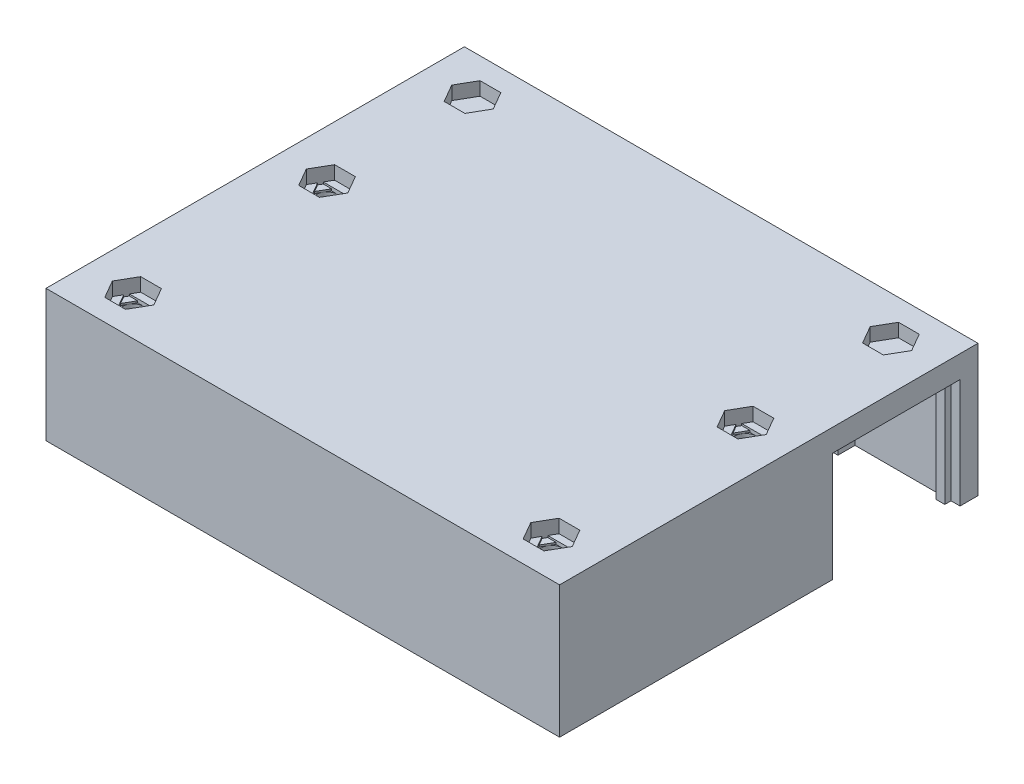
SolidWorks part; units mm, degrees
ref_plane "Front Plane" through (0, 0, 0) normal (0, 0, 1) x (1, 0, 0)
ref_plane "Top Plane" through (0, 0, 0) normal (0, 1, 0) x (1, 0, 0)
ref_plane "Right Plane" through (0, 0, 0) normal (1, 0, 0) x (0, 0, -1)
sketch "Sketch1" plane through (0, 0, 0) normal (0, 1, 0) x (1, 0, 0)
  line L0 (-5.85, 7.1) -> (-5.85, -7.1)
  line L1 (-4.85, -7.1) -> (4.85, -7.1)
  line L2 (-4.85, -7.1) -> (-4.85, 7.1)
  line L3 (-4.85, 7.1) -> (4.85, 7.1)
  line L4 (4.85, -7.1) -> (4.85, 7.1)
  line L5 (-4.85, -7.1) -> (4.85, 7.1)
  line L6 (-4.85, 7.1) -> (4.85, -7.1) construction
  line L7 (0.95, -5.2) -> (8.75, -5.2)
  line L8 (0.95, -5.2) -> (0.95, 5.2)
  line L9 (0.95, 5.2) -> (8.75, 5.2)
  line L10 (8.75, -5.2) -> (8.75, 5.2)
  line L11 (0.95, -5.2) -> (8.75, 5.2) construction
  line L12 (0.95, 5.2) -> (8.75, -5.2) construction
  line L13 (-4.85, 7.1) -> (-6.85, 7.1)
  line L14 (-4.85, 7.1) -> (-4.85, -7.1)
  line L15 (-4.85, -7.1) -> (-6.85, -7.1)
  line L16 (-6.85, 7.1) -> (-6.85, -7.1)
  line L17 (-6.85, 9.1) -> (-6.85, 7.1)
  line L18 (-6.85, 9.1) -> (6.85, 9.1)
  line L19 (6.85, 9.1) -> (6.85, 7.2)
  line L20 (6.85, 7.2) -> (10.75, 7.2)
  line L21 (10.75, 7.2) -> (10.75, -7.2)
  line L22 (10.75, -7.2) -> (6.85, -7.2)
  line L23 (6.85, -7.2) -> (6.85, -9.1)
  line L24 (6.85, -9.1) -> (-6.85, -9.1)
  line L25 (-6.85, -9.1) -> (-6.85, -7.1)
  line L26 (-4.85, 0) -> (-5.85, 0) construction
  line L27 (-5.85, 6.4) -> (-4.85, 6.4)
  line L28 (-5.85, -6.4) -> (-4.85, -6.4)
  line L29 (-5.35, -6.4) -> (-5.35, 0) construction
  line L30 (-5.35, 0) -> (-5.35, 6.4) construction
  line L31 (-5.85, 7.1) -> (-5.85, 9.1)
  line L32 (-5.85, -7.1) -> (-5.85, -9.1)
  line L33 (21.75, -9.1) -> (21.75, 5.2) construction
  line L38 (-6.85, -37.5) -> (50.35, -37.5)
  line L40 (-6.85, -37.5) -> (-6.85, -9.1)
  line L42 (-6.85, -9.1) -> (50.35, -9.1)
  line L43 (50.35, -37.5) -> (50.35, -9.1)
  line L45 (21.75, -37.5) -> (21.75, -22.3) construction
  line L47 (46.25, -11.5) -> (47.25, -11.5) construction
  line L48 (42.55, -5.2) -> (34.75, -5.2)
  line L49 (34.75, -5.2) -> (34.75, 5.2)
  line L50 (42.55, 5.2) -> (34.75, 5.2)
  line L51 (38.65, -7.1) -> (38.65, 7.1)
  line L52 (49.35, 6.4) -> (48.35, 6.4)
  line L53 (48.35, -7.1) -> (48.35, 7.1)
  line L54 (49.35, -6.4) -> (48.35, -6.4)
  line L55 (48.35, -7.1) -> (38.65, -7.1)
  line L56 (49.35, -7.1) -> (49.35, -9.1)
  line L57 (49.35, 7.1) -> (49.35, -7.1)
  line L58 (48.35, 7.1) -> (38.65, 7.1)
  line L59 (49.35, 7.1) -> (49.35, 9.1)
  line L60 (50.35, 9.1) -> (50.35, 7.1)
  line L61 (50.35, 7.1) -> (50.35, -7.1)
  line L62 (50.35, -9.1) -> (50.35, -7.1)
  line L63 (36.65, -9.1) -> (50.35, -9.1)
  line L64 (36.65, -7.2) -> (36.65, -9.1)
  line L65 (32.75, -7.2) -> (36.65, -7.2)
  line L66 (32.75, 7.2) -> (32.75, -7.2)
  line L67 (36.65, 7.2) -> (32.75, 7.2)
  line L68 (36.65, 9.1) -> (36.65, 7.2)
  line L69 (50.35, 9.1) -> (36.65, 9.1)
  line L70 (48.35, -9.1) -> (-4.85, -9.1)
  line L75 (48.35, -9.1) -> (48.35, -35.5)
  line L76 (48.35, -35.5) -> (-4.85, -35.5)
  line L81 (-4.85, -9.1) -> (-4.85, -35.5)
  line L82 (48.35, -9.1) -> (-4.85, -35.5) construction
  line L83 (48.35, -35.5) -> (-4.85, -9.1) construction
  line L84 (6.85, 9.1) -> (36.65, 9.1)
  line L85 (-1.55, -33.1) -> (45.05, -33.1) construction
  line L86 (-1.55, -33.1) -> (-1.55, -11.5) construction
  line L87 (48.35, -7.1) -> (50.35, -7.1)
  line L88 (48.35, 7.1) -> (50.35, 7.1)
  line L89 (-1.55, -11.5) -> (45.05, -11.5) construction
  line L90 (45.05, -33.1) -> (45.05, -11.5) construction
  line L91 (-1.55, -33.1) -> (45.05, -11.5) construction
  line L92 (-1.55, -11.5) -> (45.05, -33.1) construction
  line L93 (47.25, -35.3) -> (-3.75, -35.3) construction
  line L94 (47.25, -35.3) -> (47.25, -9.3) construction
  line L95 (47.25, -9.3) -> (-3.75, -9.3) construction
  line L96 (-3.75, -35.3) -> (-3.75, -9.3) construction
  line L97 (47.25, -35.3) -> (-3.75, -9.3) construction
  line L98 (47.25, -9.3) -> (-3.75, -35.3) construction
  line L99 (45.05, -10.3) -> (45.05, -9.3) construction
  line L101 (-2.55, -13.7) -> (-0.55, -13.7)
  line L102 (-2.55, -13.7) -> (-2.55, -15.7)
  line L103 (-2.55, -15.7) -> (-0.55, -15.7)
  line L104 (-0.55, -13.7) -> (-0.55, -15.7)
  line L105 (-2.55, -13.7) -> (-0.55, -15.7) construction
  line L106 (-2.55, -15.7) -> (-0.55, -13.7) construction
  line L107 (-2.55, -28.9) -> (-0.55, -28.9)
  line L108 (-2.55, -28.9) -> (-2.55, -30.9)
  line L109 (-2.55, -30.9) -> (-0.55, -30.9)
  line L110 (-0.55, -28.9) -> (-0.55, -30.9)
  line L111 (-2.55, -28.9) -> (-0.55, -30.9) construction
  line L112 (-2.55, -30.9) -> (-0.55, -28.9) construction
  line L113 (46.05, -28.9) -> (44.05, -28.9)
  line L114 (46.05, -28.9) -> (46.05, -30.9)
  line L115 (46.05, -30.9) -> (44.05, -30.9)
  line L116 (44.05, -28.9) -> (44.05, -30.9)
  line L117 (46.05, -28.9) -> (44.05, -30.9) construction
  line L118 (46.05, -30.9) -> (44.05, -28.9) construction
  line L119 (46.05, -13.7) -> (44.05, -13.7)
  line L120 (46.05, -13.7) -> (46.05, -15.7)
  line L121 (46.05, -15.7) -> (44.05, -15.7)
  line L122 (44.05, -13.7) -> (44.05, -15.7)
  line L123 (46.05, -13.7) -> (44.05, -15.7) construction
  line L124 (46.05, -15.7) -> (44.05, -13.7) construction
  line L125 (45.05, -29.9) -> (-1.55, -29.9)
  line L126 (45.05, -29.9) -> (45.05, -14.7)
  line L127 (45.05, -14.7) -> (-1.55, -14.7)
  line L128 (-1.55, -29.9) -> (-1.55, -14.7)
  line L129 (45.05, -29.9) -> (-1.55, -14.7) construction
  line L130 (45.05, -14.7) -> (-1.55, -29.9) construction
  circle A0 centre (-1.55, -11.5) radius 1.2
  circle A1 centre (-1.55, -33.1) radius 1.2
  circle A2 centre (45.05, -33.1) radius 1.2
  circle A3 centre (45.05, -11.5) radius 1.2
  point P0 (0, 0)
  point P6 (4.85, 0)
  point P88 (-1.55, -14.7)
  point P93 (-1.55, -29.9)
  point P98 (45.05, -29.9)
  point P103 (45.05, -14.7)
  point P108 (45.05, -17.403)
  point P109 (45.05, -27.197)
  point P114 (-1.55, -27.197)
  dimension "D20" = 2
  dimension "D21" = 2.4
  dimension "D22" = 51
  dimension "D24" = 1
  dimension "D1" = 14.2
  dimension "D2" = 9.7
  dimension "D3" = 10.4
  dimension "D4" = 3.9
  dimension "D5" = 11.7
  dimension "D6" = 1
  dimension "D7" = 2
  dimension "D8" = 2
  dimension "D9" = 2
  dimension "D10" = 2
  dimension "D11" = 2
  dimension "D12" = 2
  dimension "D13" = 57.2
  dimension "D14" = 12.8
  dimension "D15" = 0
  dimension "D16" = 28.4
  dimension "D17" = 2
  dimension "D18" = 2
  dimension "D19" = 26.4
  dimension "D23" = 26
  dimension "D25" = 2
  dimension "D26" = 2.2
extrude "Boss-Extrude1" add sketch "Sketch1" along normal blind 2 contours L15 L32 L24 L23 L22 L21 L20 L19 L18 L31 L13 L3 L4 L9 L10 L7 L1 | L13 L31 L18 L17 | L13 L16 L15 L0 | L32 L15 L25 L24 | L0 L28 L14 L27 | L28 L0 L15 L2 | L0 L27 L14 L13 | L8 L9 L5 L3 L14 L2 | L7 L8 L5 L1 L4 | L9 L5 L8 L7 L4 | L9 L8 L5 | L5 L9 L4 | L7 L10 L9 L4 | L84 L19 L20 L21 L22 L23 L42 L64 L65 L66 L67 L68 | L58 L88 L59 L69 L68 L67 L66 L65 L64 L42 L56 L87 L55 L51 L48 L49 L50 | L48 L51 L50 L49 | L53 L58 L51 L55 | L57 L52 L53 L54 | L88 L57 L87 L61 | L59 L88 L60 L69 | L87 L56 L42 L62 | L53 L87 L57 L54 | L88 L53 L52 L57 | L42 L76 L81 L70 L75 L24 L40 L38 L43 | A3 A2 L85 L76 L75 L70 L81 A1 | A1 L85 A2 A3 | L76 L85 | L42 L76 | L128 L107 L110 L125 L116 L113 L126 L121 L122 L127 L104 L103 | L103 L128 L127 L104 L101 L102 | L125 L128 L107 L108 L109 L110 | L128 L125 L110 L107 | L128 L103 L104 L127 | L127 L126 L121 L120 L119 L122 | L126 L127 L122 L121 | L126 L125 L116 L115 L114 L113 | L125 L126 L113 L116 region at (-5.35, 0, -6.75) region at (-5.6037, 0, -8.1) region at (-6.35, 0, 0) region at (-6.35, 0, -8.1) region at (-5.35, 0, 0) region at (-1.883, 0, -2.2454) region at (-5.35, 0, 6.75) region at (4.4174, 0, -5.8333) region at (-6.35, 0, 8.1) region at (21.75, 0, 0) region at (6.8, 0, 0) region at (3.0507, 0, 0.5471) region at (1.8174, 0, -3.9302) region at (-6.35, 0, 9.7386) region at (43, 0, -8.8537) region at (-0.085, 0, 4.7047) region at (49.85, 0, -8.1) region at (1, 0, 9.6939) region at (49.85, 0, 0) region at (48.85, 0, -6.75) region at (49.85, 0, 8.1) region at (48.85, 0, 0) region at (43.5, 0, 0) region at (48.85, 0, 6.75) region at (36.7, 0, 0) region at (-1.7167, 0, 14.5333) region at (21.75, 0, 22.3) region at (-1.05, 0, 15.2) region at (44.55, 0, 15.2) region at (45.2167, 0, 14.5333) region at (-1.7167, 0, 30.0667) region at (-1.05, 0, 29.4) region at (44.55, 0, 29.4) region at (45.2167, 0, 30.0667)
extrude "Boss-Extrude2" add sketch "Sketch1<5>" against normal blind 12.2 contours L15 L32 L24 L23 L22 L21 L20 L19 L18 L31 L13 L3 L4 L9 L10 L7 L1 | L0 L27 L14 L13 | L28 L0 L15 L2 | L13 L31 L18 L17 | L32 L15 L25 L24 | L58 L88 L59 L69 L68 L67 L66 L65 L64 L42 L56 L87 L55 L51 L48 L49 L50 | L59 L88 L60 L69 | L87 L56 L42 L62 | L88 L53 L52 L57 | L53 L87 L57 L54 region at (-5.35, 0, -6.75) region at (-5.6037, 0, -8.1) region at (-6.35, 0, -8.1) region at (-5.35, 0, 6.75) region at (-6.35, 0, 8.1) region at (43, 0, -8.8537) region at (49.85, 0, -8.1) region at (48.85, 0, -6.75) region at (49.85, 0, 8.1) region at (48.85, 0, 6.75)
sketch "Sketch1<5>" plane through (0, 0, 0) normal (0, 1, 0) x (1, 0, 0) same geometry as "Sketch1"
extrude "Boss-Extrude3" add sketch "Sketch1<6>" against normal blind 1.8 contours L7 L10 L9 L4 | L48 L51 L50 L49 region at (6.8, 0, 0) region at (36.7, 0, 0)
sketch "Sketch1<6>" plane through (0, 0, 0) normal (0, 1, 0) x (1, 0, 0) same geometry as "Sketch1"
sketch "Sketch3" plane through (8.75, 0, 0) normal (-1, 0, 0) x (0, 0, 1)
  line L0 (-3.9961, -3.8971) -> (-0.602, -3.8971) construction
  line L1 (-2.299, -2.2) -> (-2.299, -5.5941) construction
  line L2 (0.602, -3.8971) -> (3.9961, -3.8971) construction
  line L3 (2.299, -2.2) -> (2.299, -5.5941) construction
  line L4 (-3.9961, -3.8971) -> (-2.299, -2.2)
  line L5 (-0.602, -3.8971) -> (-2.299, -2.2)
  line L6 (-2.299, -5.5941) -> (-0.602, -3.8971)
  line L7 (-3.9961, -3.8971) -> (-2.299, -5.5941)
  line L8 (2.299, -5.5941) -> (0.602, -3.8971)
  line L9 (0.602, -3.8971) -> (2.299, -2.2)
  line L10 (3.9961, -3.8971) -> (2.299, -2.2)
  line L11 (2.299, -5.5941) -> (3.9961, -3.8971)
  line L12 (-5.2, -3.8971) -> (-3.9961, -3.8971) construction
  line L13 (-5.2, -12.2) -> (-5.2, -1.8) construction
  line L14 (-0.602, -3.8971) -> (0.602, -3.8971) construction
  line L15 (3.9961, -3.8971) -> (5.2, -3.8971) construction
  line L16 (5.2, -12.2) -> (5.2, -1.8) construction
  line L17 (-2.299, -2.2) -> (-2.299, -1.8)
  line L18 (5.2, -1.8) -> (-5.2, -1.8) construction
  line L19 (-0.802, -3.6971) -> (0.802, -3.6971)
  line L20 (-0.802, -4.0971) -> (0.802, -4.0971)
  point P8 (-2.299, -3.8971)
  point P9 (-2.299, -3.8971)
  point P10 (2.299, -3.8971)
  point P11 (2.299, -3.8971)
  dimension "D1" = 2.4
  dimension "D2" = 0.4
  dimension "D3" = 0.2
extrude "Cut-Extrude1" cut sketch "Sketch3" against normal blind 100 contours L4 L7 L6 L5 | L8 L11 L10 L9 region at (8.75, -3.8971, -2.299) region at (8.75, -3.8971, 2.299)
extrude "Boss-Extrude4" add sketch "Sketch1<9>" against normal blind 12.2 contours L81 L42 L24 L40 L38 L43 L63 L75 L76 region at (-6.35, 0, 9.7386)
sketch "Sketch1<9>" plane through (0, 0, 0) normal (0, 1, 0) x (1, 0, 0) same geometry as "Sketch1"
extrude "Boss-Extrude5" add sketch "Sketch1<10>" against normal blind 2 contours L127 L126 L121 L120 L119 L122 | L126 L127 L122 L121 | L126 L125 L116 L115 L114 L113 | L125 L126 L113 L116 | L103 L128 L127 L104 L101 L102 | L128 L103 L104 L127 | L125 L128 L107 L108 L109 L110 | L128 L125 L110 L107 region at (-1.7167, 0, 14.5333) region at (-1.05, 0, 15.2) region at (44.55, 0, 15.2) region at (45.2167, 0, 14.5333) region at (-1.7167, 0, 30.0667) region at (-1.05, 0, 29.4) region at (44.55, 0, 29.4) region at (45.2167, 0, 30.0667)
sketch "Sketch1<10>" plane through (0, 0, 0) normal (0, 1, 0) x (1, 0, 0) same geometry as "Sketch1"
sketch "Sketch4" plane through (0, 2, 0) normal (0, 1, 0) x (1, 0, 0)
  line L0 (-1.55, -33.1) -> (-1.55, -37.5) construction
  line L1 (-0.3953, -31.1) -> (-2.7047, -31.1)
  line L2 (-2.7047, -31.1) -> (-3.8594, -33.1)
  line L3 (-3.8594, -33.1) -> (-2.7047, -35.1)
  line L4 (-2.7047, -35.1) -> (-0.3953, -35.1)
  line L5 (-0.3953, -35.1) -> (0.7594, -33.1)
  line L6 (0.7594, -33.1) -> (-0.3953, -31.1)
  line L7 (-0.3953, -9.5) -> (-2.7047, -9.5)
  line L8 (-2.7047, -9.5) -> (-3.8594, -11.5)
  line L9 (-3.8594, -11.5) -> (-2.7047, -13.5)
  line L10 (-2.7047, -13.5) -> (-0.3953, -13.5)
  line L11 (-0.3953, -13.5) -> (0.7594, -11.5)
  line L12 (0.7594, -11.5) -> (-0.3953, -9.5)
  line L13 (46.2047, -9.5) -> (43.8953, -9.5)
  line L14 (43.8953, -9.5) -> (42.7406, -11.5)
  line L15 (42.7406, -11.5) -> (43.8953, -13.5)
  line L16 (43.8953, -13.5) -> (46.2047, -13.5)
  line L17 (46.2047, -13.5) -> (47.3594, -11.5)
  line L18 (47.3594, -11.5) -> (46.2047, -9.5)
  line L19 (46.2047, -31.1) -> (43.8953, -31.1)
  line L20 (43.8953, -31.1) -> (42.7406, -33.1)
  line L21 (42.7406, -33.1) -> (43.8953, -35.1)
  line L22 (43.8953, -35.1) -> (46.2047, -35.1)
  line L23 (46.2047, -35.1) -> (47.3594, -33.1)
  line L24 (47.3594, -33.1) -> (46.2047, -31.1)
  line L25 (-6.85, -37.5) -> (50.35, -37.5) construction
  line L26 (-1.55, 4.7) -> (45.05, 4.7) construction
  line L27 (-1.55, 4.7) -> (-6.85, 4.7) construction
  line L28 (-6.85, 9.1) -> (-6.85, -37.5) construction
  line L29 (-1.55, 4.7) -> (-1.55, 9.1) construction
  line L30 (-6.85, 9.1) -> (50.35, 9.1) construction
  line L31 (21.75, 4.7) -> (21.75, 9.1) construction
  line L32 (-1.55, -33.1) -> (-6.85, -33.1) construction
  line L34 (-0.3953, 6.7) -> (-2.7047, 6.7)
  line L35 (-2.7047, 6.7) -> (-3.8594, 4.7)
  line L36 (-3.8594, 4.7) -> (-2.7047, 2.7)
  line L37 (-2.7047, 2.7) -> (-0.3953, 2.7)
  line L38 (-0.3953, 2.7) -> (0.7594, 4.7)
  line L39 (0.7594, 4.7) -> (-0.3953, 6.7)
  line L40 (46.2047, 6.7) -> (43.8953, 6.7)
  line L41 (43.8953, 6.7) -> (42.7406, 4.7)
  line L42 (42.7406, 4.7) -> (43.8953, 2.7)
  line L43 (43.8953, 2.7) -> (46.2047, 2.7)
  line L44 (46.2047, 2.7) -> (47.3594, 4.7)
  line L45 (47.3594, 4.7) -> (46.2047, 6.7)
  line L46 (0.413, -8.1) -> (-3.513, -8.1)
  line L47 (-3.513, -8.1) -> (-5.476, -11.5)
  line L48 (-5.476, -11.5) -> (-3.513, -14.9)
  line L49 (-3.513, -14.9) -> (0.413, -14.9)
  line L50 (0.413, -14.9) -> (2.376, -11.5)
  line L51 (2.376, -11.5) -> (0.413, -8.1)
  line L52 (43.087, -8.1) -> (41.124, -11.5)
  line L53 (41.124, -11.5) -> (43.087, -14.9)
  line L54 (43.087, -14.9) -> (47.013, -14.9)
  line L55 (47.013, -14.9) -> (48.976, -11.5)
  line L56 (48.976, -11.5) -> (47.013, -8.1)
  line L57 (47.013, -8.1) -> (43.087, -8.1)
  line L58 (43.087, 8.1) -> (41.124, 4.7)
  line L59 (41.124, 4.7) -> (43.087, 1.3)
  line L60 (43.087, 1.3) -> (47.013, 1.3)
  line L61 (47.013, 1.3) -> (48.976, 4.7)
  line L62 (48.976, 4.7) -> (47.013, 8.1)
  line L63 (47.013, 8.1) -> (43.087, 8.1)
  line L64 (0.413, 8.1) -> (-3.513, 8.1)
  line L65 (-3.513, 8.1) -> (-5.476, 4.7)
  line L66 (-5.476, 4.7) -> (-3.513, 1.3)
  line L67 (-3.513, 1.3) -> (0.413, 1.3)
  line L68 (0.413, 1.3) -> (2.376, 4.7)
  line L69 (2.376, 4.7) -> (0.413, 8.1)
  line L70 (0.413, -29.7) -> (-3.513, -29.7)
  line L71 (-3.513, -29.7) -> (-5.476, -33.1)
  line L72 (-5.476, -33.1) -> (-3.513, -36.5)
  line L73 (-3.513, -36.5) -> (0.413, -36.5)
  line L74 (0.413, -36.5) -> (2.376, -33.1)
  line L75 (2.376, -33.1) -> (0.413, -29.7)
  line L76 (43.087, -29.7) -> (41.124, -33.1)
  line L77 (41.124, -33.1) -> (43.087, -36.5)
  line L78 (43.087, -36.5) -> (47.013, -36.5)
  line L79 (47.013, -36.5) -> (48.976, -33.1)
  line L80 (48.976, -33.1) -> (47.013, -29.7)
  line L81 (47.013, -29.7) -> (43.087, -29.7)
  circle A0 centre (-1.55, -33.1) radius 2 construction
  circle A1 centre (-1.55, -11.5) radius 2 construction
  circle A2 centre (45.05, -11.5) radius 2 construction
  circle A3 centre (45.05, -33.1) radius 2 construction
  circle A4 centre (-1.55, 4.7) radius 1.2
  circle A5 centre (45.05, 4.7) radius 1.2
  circle A8 centre (-1.55, 4.7) radius 2 construction
  circle A9 centre (45.05, 4.7) radius 2 construction
  circle A10 centre (-1.55, -11.5) radius 3.4 construction
  circle A11 centre (45.05, -11.5) radius 3.4 construction
  circle A12 centre (45.05, 4.7) radius 3.4 construction
  circle A13 centre (-1.55, 4.7) radius 3.4 construction
  circle A14 centre (-1.55, -33.1) radius 3.4 construction
  circle A15 centre (45.05, -33.1) radius 3.4 construction
  line M21 (50.35, -37.5) -> (50.35, 9.1)
  line M22 (50.35, 9.1) -> (-6.85, 9.1)
  line M23 (-6.85, 9.1) -> (-6.85, -37.5)
  line M24 (-6.85, -37.5) -> (50.35, -37.5)
  circle M25 centre (45.05, -11.5) radius 1.2
  circle M26 centre (45.05, -33.1) radius 1.2
  circle M27 centre (-1.55, -33.1) radius 1.2
  circle M28 centre (-1.55, -11.5) radius 1.2
  dimension "D1" = 2.4
  dimension "D2" = 2.4
  dimension "D3" = 5.3
  dimension "D4" = 4.4
  dimension "D5" = 4
  dimension "D6" = 1.4
extrude "Boss-Extrude6" add sketch "Sketch4" along normal blind 0.5 contours L81 L80 L79 L78 L77 L76 L75 L74 L73 L72 L71 L70 L69 L68 L67 L66 L65 L64 L63 L62 L61 L60 L59 L58 L57 L56 L55 L54 L53 L52 L51 L50 L49 L48 L47 L46 M24 M21 M22 M23 | L68 L69 L64 L65 L66 L67 L39 L38 L37 L36 L35 L34 | L62 L63 L58 L59 L60 L61 L45 L44 L43 L42 L41 L40 | L56 L57 L52 L53 L54 L55 L18 L17 L16 L15 L14 L13 | L80 L81 L76 L77 L78 L79 L24 L23 L22 L21 L20 L19 | L74 L75 L70 L71 L72 L73 L6 L5 L4 L3 L2 L1 | L50 L51 L46 L47 L48 L49 L12 L11 L10 L9 L8 L7 region at (1.3045, 2, 9.8519) region at (45.05, 2, 8.2039) region at (45.05, 2, -7.9961) region at (1.3045, 2, -6.3481) region at (1.3045, 2, 31.4519) region at (45.05, 2, 29.8039) region at (21.75, 2, 14.2892)
extrude "Cut-Extrude2" cut sketch "Sketch4<3>" against normal blind 1 contours L38 L39 L34 L35 L36 L37 A4 | L44 L45 L40 L41 L42 L43 A5 | L17 L18 L13 L14 L15 L16 M25 | L11 L12 L7 L8 L9 L10 M28 | L5 L6 L1 L2 L3 L4 M27 | L23 L24 L19 L20 L21 L22 M26 | A4 | A5 | M25 | M28 | M27 | M26 region at (0.1291, 2, 32.1306) region at (0.1291, 2, 10.5306) region at (46.7291, 2, 10.5306) region at (46.7291, 2, 32.1306) region at (0.1291, 2, -5.6694) region at (46.7291, 2, -5.6694) region at (-1.55, 2, -4.7) region at (45.05, 2, -4.7) region at (45.05, 2, 11.5) region at (45.05, 2, 33.1) region at (-1.55, 2, 33.1) region at (-1.55, 2, 11.5)
sketch "Sketch4<3>" plane through (0, 2, 0) normal (0, 1, 0) x (1, 0, 0) same geometry as "Sketch4"
sketch "Sketch5" plane through (0, 1, 0) normal (0, 1, 0) x (1, 0, 0)
  line L0 (-0.3953, -9.5) -> (-2.7047, -9.5) construction
  line L5 (-1.55, -9.1) -> (-3.6285, -12.7)
  line L6 (-3.6285, -12.7) -> (0.5285, -12.7)
  line L11 (0.5285, -12.7) -> (-1.55, -9.1)
  line L12 (-3.6285, -10.3) -> (-1.55, -13.9)
  line L13 (-1.55, -13.9) -> (0.5285, -10.3)
  line L14 (0.5285, -10.3) -> (-3.6285, -10.3)
  line L15 (-0.3953, -9.5) -> (-2.7047, -9.5)
  line L16 (-2.7047, -9.5) -> (-3.8594, -11.5)
  line L17 (-3.8594, -11.5) -> (-2.7047, -13.5)
  line L18 (-2.7047, -13.5) -> (-0.3953, -13.5)
  line L19 (-0.3953, -13.5) -> (0.7594, -11.5)
  line L20 (0.7594, -11.5) -> (-0.3953, -9.5)
  line L21 (21.75, 9.1) -> (21.75, -37.5) construction
  line L22 (50.35, 9.1) -> (-6.85, 9.1) construction
  line L23 (-6.85, -37.5) -> (50.35, -37.5) construction
  line L24 (-1.55, -11.5) -> (-1.55, -33.1) construction
  line L25 (45.05, -35.5) -> (47.1285, -31.9)
  line L26 (47.1285, -31.9) -> (42.9715, -31.9)
  line L27 (45.05, -11.5) -> (45.05, -33.1) construction
  line L28 (42.7406, -11.5) -> (43.8953, -9.5)
  line L29 (43.8953, -13.5) -> (42.7406, -11.5)
  line L30 (46.2047, -13.5) -> (43.8953, -13.5)
  line L31 (47.3594, -11.5) -> (46.2047, -13.5)
  line L32 (46.2047, -9.5) -> (47.3594, -11.5)
  line L33 (43.8953, -9.5) -> (46.2047, -9.5)
  line L34 (42.9715, -10.3) -> (47.1285, -10.3)
  line L35 (45.05, -13.9) -> (42.9715, -10.3)
  line L36 (47.1285, -10.3) -> (45.05, -13.9)
  line L37 (42.9715, -12.7) -> (45.05, -9.1)
  line L38 (47.1285, -12.7) -> (42.9715, -12.7)
  line L39 (45.05, -9.1) -> (47.1285, -12.7)
  line L40 (-1.55, -22.3) -> (45.05, -22.3) construction
  line L41 (42.9715, -31.9) -> (45.05, -35.5)
  line L42 (47.1285, -34.3) -> (45.05, -30.7)
  line L43 (45.05, -30.7) -> (42.9715, -34.3)
  line L44 (42.9715, -34.3) -> (47.1285, -34.3)
  line L45 (43.8953, -35.1) -> (46.2047, -35.1)
  line L46 (46.2047, -35.1) -> (47.3594, -33.1)
  line L47 (47.3594, -33.1) -> (46.2047, -31.1)
  line L48 (46.2047, -31.1) -> (43.8953, -31.1)
  line L49 (43.8953, -31.1) -> (42.7406, -33.1)
  line L50 (42.7406, -33.1) -> (43.8953, -35.1)
  line L51 (0.7594, -33.1) -> (-0.3953, -35.1)
  line L52 (-0.3953, -31.1) -> (0.7594, -33.1)
  line L53 (-2.7047, -31.1) -> (-0.3953, -31.1)
  line L54 (-3.8594, -33.1) -> (-2.7047, -31.1)
  line L55 (-2.7047, -35.1) -> (-3.8594, -33.1)
  line L56 (-0.3953, -35.1) -> (-2.7047, -35.1)
  line L57 (0.5285, -34.3) -> (-3.6285, -34.3)
  line L58 (-1.55, -30.7) -> (0.5285, -34.3)
  line L59 (-3.6285, -34.3) -> (-1.55, -30.7)
  line L60 (0.5285, -31.9) -> (-1.55, -35.5)
  line L61 (-3.6285, -31.9) -> (0.5285, -31.9)
  line L62 (-1.55, -35.5) -> (-3.6285, -31.9)
  circle A0 centre (45.05, -33.1) radius 1.2 construction
  circle A1 centre (-1.55, -11.5) radius 1.2 construction
  circle A2 centre (-1.55, -11.5) radius 1.2 construction
  circle A3 centre (-1.55, -11.5) radius 1.2 construction
  circle A4 centre (-1.55, -11.5) radius 2 construction
  circle A5 centre (45.05, -11.5) radius 2 construction
  circle A6 centre (45.05, -11.5) radius 1.2 construction
  circle A7 centre (45.05, -11.5) radius 1.2 construction
  circle A8 centre (45.05, -33.1) radius 1.2 construction
  circle A9 centre (45.05, -33.1) radius 2 construction
  circle A10 centre (-1.55, -33.1) radius 2 construction
  circle A11 centre (-1.55, -33.1) radius 1.2 construction
  circle A12 centre (-1.55, -33.1) radius 1.2 construction
  circle M11 centre (-1.55, -11.5) radius 1.2
  line M13 (0.7594, -11.5) -> (-0.3953, -9.5)
  line M15 (-2.7047, -9.5) -> (-3.8594, -11.5)
  line M17 (-2.7047, -13.5) -> (-0.3953, -13.5)
  dimension "D1" = 0
extrude "Cut-Extrude4" cut sketch "Sketch5<5>" against normal blind 0.2 contours L12 L6 M11 | L6 L13 M11 | L13 L11 M11 | L11 L14 M11 | L14 L5 M11 | L5 L12 M11 | L5 L14 L12 M15 | L14 L11 L13 M13 | L13 L6 L12 M17 | L39 L34 L37 L35 L38 L36 | L34 L39 L36 L32 | L35 L37 L34 L28 | L36 L38 L35 L30 | L41 L44 L25 L42 L26 L43 | L26 L49 L41 L43 | L25 L47 L26 L42 | L41 L45 L25 L44 | L62 L57 L60 L58 L61 L59 | L62 L59 L61 L54 | L61 L58 L60 L52 | L62 L56 L60 L57 region at (-2.1701, 1, 10.4259) region at (-2.8779, 1, 10.7333) region at (-0.2221, 1, 10.7333) region at (-0.9299, 1, 10.4259) region at (-2.7903, 1, 11.5) region at (-0.3097, 1, 11.5) region at (-2.1701, 1, 12.5741) region at (-1.55, 1, 13.0333) region at (-0.9299, 1, 12.5741) region at (45.05, 1, 34.6333) region at (45.05, 1, 33.1) region at (46.3779, 1, 32.3333) region at (43.7221, 1, 32.3333) region at (43.7221, 1, 10.7333) region at (45.05, 1, 11.5) region at (45.05, 1, 13.0333) region at (46.3779, 1, 10.7333) region at (-0.2221, 1, 32.3333) region at (-1.55, 1, 33.1) region at (-1.55, 1, 34.6333) region at (-2.8779, 1, 32.3333)
sketch "Sketch5<5>" plane through (0, 1, 0) normal (0, 1, 0) x (1, 0, 0) same geometry as "Sketch5"
extrude "Cut-Extrude5" cut sketch "Sketch5" against normal blind 0.4 contours L14 L5 M11 | L11 L14 M11 | L13 L11 M11 | L6 L13 M11 | L12 L6 M11 | L5 L12 M11 | L39 L34 L37 L35 L38 L36 | L41 L44 L25 L42 L26 L43 | L62 L57 L60 L58 L61 L59 region at (-2.1701, 1, 10.4259) region at (-0.9299, 1, 10.4259) region at (-2.7903, 1, 11.5) region at (-0.3097, 1, 11.5) region at (-2.1701, 1, 12.5741) region at (-0.9299, 1, 12.5741) region at (45.05, 1, 33.1) region at (45.05, 1, 11.5) region at (-1.55, 1, 33.1)
